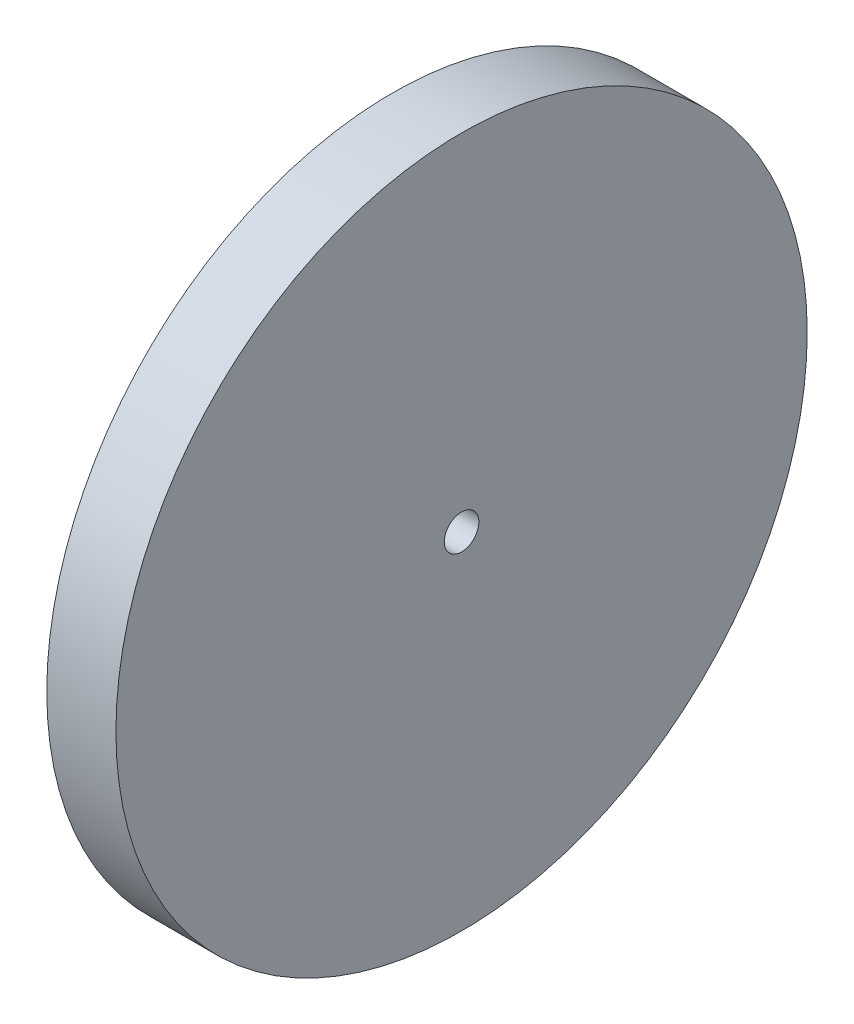
SolidWorks part; units mm, degrees
ref_plane "Front Plane" through (0, 0, 0) normal (0, 0, 1) x (1, 0, 0)
ref_plane "Top Plane" through (0, 0, 0) normal (0, 1, 0) x (1, 0, 0)
ref_plane "Right Plane" through (0, 0, 0) normal (1, 0, 0) x (0, 0, -1)
sketch "Esquisse1" plane through (0, 0, 0) normal (1, 0, 0) x (0, 0, -1)
  circle A0 centre (0, 0) radius 50
  dimension "D1" = 100
extrude "Boss.-Extru.1" add sketch "Esquisse1" along normal blind 5 and the other way blind 5 contours A0
ref_plane "Plan1" through (5, 0, 0) normal (1, 0, 0) x (0, 0, -1)
sketch "Esquisse3" plane through (5, 0, 0) normal (1, 0, 0) x (0, 0, -1)
  circle A0 centre (0, 0) radius 2.5
  dimension "D1" = 5
extrude "Enlèv. mat.-Extru.2" cut sketch "Esquisse3" against normal through all
